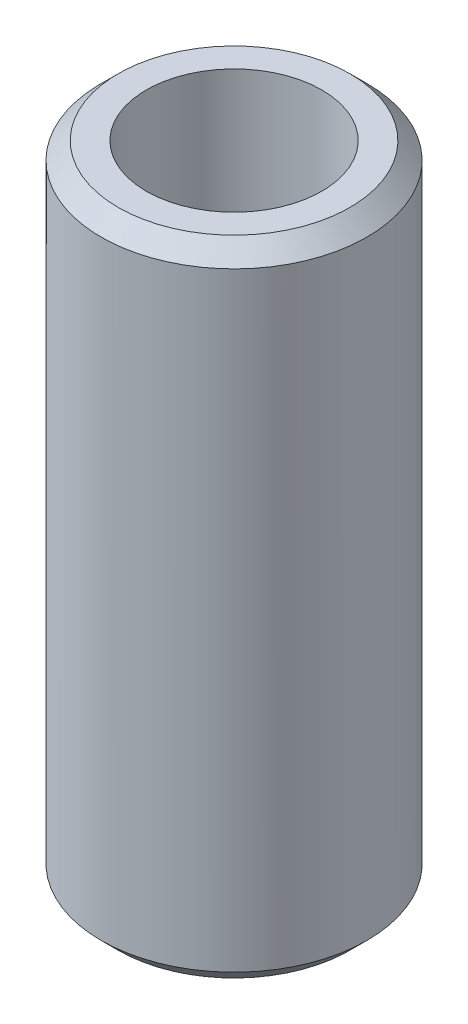
SolidWorks part; units mm, degrees
ref_plane "Front Plane" through (0, 0, 0) normal (0, 0, 1) x (1, 0, 0)
ref_plane "Top Plane" through (0, 0, 0) normal (0, 1, 0) x (1, 0, 0)
ref_plane "Right Plane" through (0, 0, 0) normal (1, 0, 0) x (0, 0, -1)
sketch "Sketch1" plane through (0, 0, 0) normal (0, 1, 0) x (1, 0, 0)
  circle A0 centre (0, 0) radius 30
  dimension "SHAFT_OD" = 60
extrude "Boss-Extrude1" add sketch "Sketch1" along normal blind 145.1354
sketch "Sketch2" plane through (0, 0, 0) normal (0, 1, 0) x (1, 0, 0)
  circle A0 centre (0, 0) radius 19.8055
  dimension "BORE_D" = 39.611
extrude "Cut-Extrude1" cut sketch "Sketch2" along normal through all
chamfer "Chamfer1" distance 3.8591 angle 45 2 edges at (0, 145.1354, 30) (0, 0, 30)
